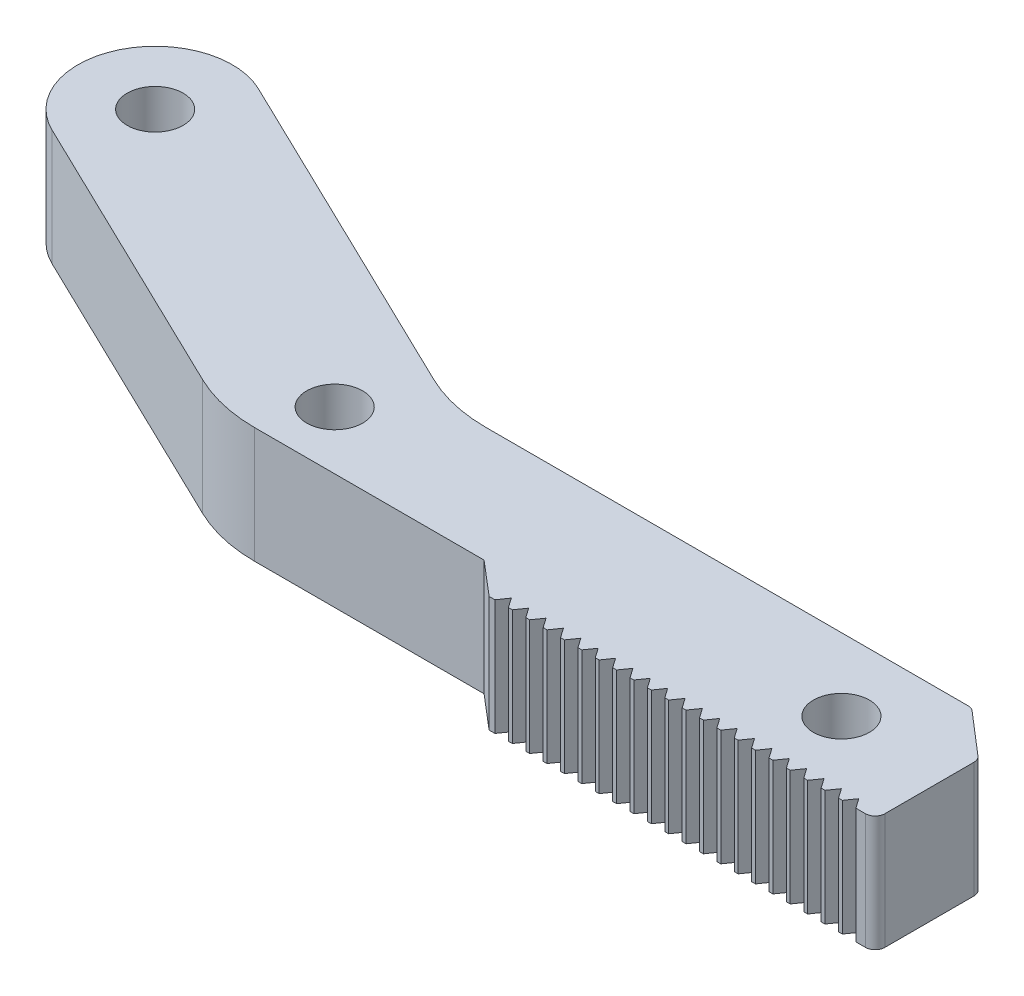
SolidWorks part; units mm, degrees
ref_plane "Alzado" through (0, 0, 0) normal (0, 0, 1) x (1, 0, 0)
ref_plane "Planta" through (0, 0, 0) normal (0, 1, 0) x (1, 0, 0)
ref_plane "Vista lateral" through (0, 0, 0) normal (1, 0, 0) x (0, 0, -1)
sketch "Croquis base" plane through (0, 0, 0) normal (0, 1, 0) x (1, 0, 0)
  line L0 (16.2564, 0) -> (-16.2436, 0) construction
  line L1 (-5.5056, -3) -> (-16.2436, -3)
  line L2 (16.2564, -3) -> (16.2564, 0.85)
  line L3 (13.7564, 3) -> (-13.2589, 3)
  line L5 (-16.2436, 0) -> (-34.25, 8.7046) construction
  line L6 (-16.2436, 0) -> (-34.25, 0) construction
  line L7 (-32.5091, 12.3059) -> (-13.2589, 3)
  line L8 (-35.9909, 5.1033) -> (-19.2283, -3)
  line L9 (-16.2436, -3) -> (-19.2283, -3)
  line L10 (16.2564, -3) -> (16.2564, -4.5)
  line L11 (16.2564, -4.5) -> (-3.7436, -4.5) construction
  line L12 (-3.7436, -4.5) -> (-3.7436, -3) construction
  line L13 (15.2564, -4.5) -> (14.9064, -4)
  line L14 (14.9064, -4) -> (14.5564, -4.5)
  line L15 (15.2564, -4.5) -> (16.2564, -4.5)
  line L16 (14.5564, -4.5) -> (14.3564, -4.5)
  line L17 (14.0064, -4) -> (13.6564, -4.5)
  line L18 (13.6564, -4.5) -> (13.4564, -4.5)
  line L19 (14.3564, -4.5) -> (14.0064, -4)
  line L20 (13.1064, -4) -> (12.7564, -4.5)
  line L21 (12.7564, -4.5) -> (12.5564, -4.5)
  line L22 (13.4564, -4.5) -> (13.1064, -4)
  line L23 (12.2064, -4) -> (11.8564, -4.5)
  line L24 (11.8564, -4.5) -> (11.6564, -4.5)
  line L25 (12.5564, -4.5) -> (12.2064, -4)
  line L26 (11.3064, -4) -> (10.9564, -4.5)
  line L27 (10.9564, -4.5) -> (10.7564, -4.5)
  line L28 (11.6564, -4.5) -> (11.3064, -4)
  line L29 (10.4064, -4) -> (10.0564, -4.5)
  line L30 (10.0564, -4.5) -> (9.8564, -4.5)
  line L31 (10.7564, -4.5) -> (10.4064, -4)
  line L32 (9.5064, -4) -> (9.1564, -4.5)
  line L33 (9.1564, -4.5) -> (8.9564, -4.5)
  line L34 (9.8564, -4.5) -> (9.5064, -4)
  line L35 (8.6064, -4) -> (8.2564, -4.5)
  line L36 (8.2564, -4.5) -> (8.0564, -4.5)
  line L37 (8.9564, -4.5) -> (8.6064, -4)
  line L38 (7.7064, -4) -> (7.3564, -4.5)
  line L39 (7.3564, -4.5) -> (7.1564, -4.5)
  line L40 (8.0564, -4.5) -> (7.7064, -4)
  line L41 (6.8064, -4) -> (6.4564, -4.5)
  line L42 (6.4564, -4.5) -> (6.2564, -4.5)
  line L43 (7.1564, -4.5) -> (6.8064, -4)
  line L44 (5.9064, -4) -> (5.5564, -4.5)
  line L45 (5.5564, -4.5) -> (5.3564, -4.5)
  line L46 (6.2564, -4.5) -> (5.9064, -4)
  line L47 (5.0064, -4) -> (4.6564, -4.5)
  line L48 (4.6564, -4.5) -> (4.4564, -4.5)
  line L49 (5.3564, -4.5) -> (5.0064, -4)
  line L50 (4.1064, -4) -> (3.7564, -4.5)
  line L51 (3.7564, -4.5) -> (3.5564, -4.5)
  line L52 (4.4564, -4.5) -> (4.1064, -4)
  line L53 (3.2064, -4) -> (2.8564, -4.5)
  line L54 (2.8564, -4.5) -> (2.6564, -4.5)
  line L55 (3.5564, -4.5) -> (3.2064, -4)
  line L56 (2.3064, -4) -> (1.9564, -4.5)
  line L57 (1.9564, -4.5) -> (1.7564, -4.5)
  line L58 (2.6564, -4.5) -> (2.3064, -4)
  line L59 (1.4064, -4) -> (1.0564, -4.5)
  line L60 (1.0564, -4.5) -> (0.8564, -4.5)
  line L61 (1.7564, -4.5) -> (1.4064, -4)
  line L62 (0.5064, -4) -> (0.1564, -4.5)
  line L63 (0.1564, -4.5) -> (-0.0436, -4.5)
  line L64 (0.8564, -4.5) -> (0.5064, -4)
  line L65 (-0.3936, -4) -> (-0.7436, -4.5)
  line L66 (-0.7436, -4.5) -> (-0.9436, -4.5)
  line L67 (-0.0436, -4.5) -> (-0.3936, -4)
  line L68 (-1.2936, -4) -> (-1.6436, -4.5)
  line L69 (-1.6436, -4.5) -> (-1.8436, -4.5)
  line L70 (-0.9436, -4.5) -> (-1.2936, -4)
  line L71 (-2.1936, -4) -> (-2.5436, -4.5)
  line L72 (-2.5436, -4.5) -> (-2.7436, -4.5)
  line L73 (-1.8436, -4.5) -> (-2.1936, -4)
  line L74 (-3.0936, -4) -> (-3.4436, -4.5)
  line L75 (-3.4436, -4.5) -> (-3.6436, -4.5)
  line L76 (-2.7436, -4.5) -> (-3.0936, -4)
  line L77 (14.9064, -4) -> (14.0064, -4) construction
  line L78 (-3.6436, -4.5) -> (-3.7436, -4.5)
  line L79 (-3.7436, -4.5) -> (-5.5056, -3)
  line L80 (16.2564, -4.5) -> (16.2564, -3)
  line L81 (-5.5056, -3) -> (16.2564, -3) construction
  line L82 (13.7564, 3) -> (16.2564, 0.85)
  arc A0 (-32.5091, 12.3059) -> (-35.9909, 5.1033) centre (-34.25, 8.7046) ccw
  circle A1 centre (-34.25, 8.7046) radius 1.45
  circle A2 centre (-16.2436, 0) radius 1.45
  circle A3 centre (10.7564, -0.75) radius 1.45
  point P0 (0, 0)
  dimension "D8" = 21.3815
  dimension "D9" = 4
  dimension "D19" = 2.9
  dimension "D1" = 6
  dimension "D2" = 32.5
  dimension "D3" = 20
  dimension "D4" = 18.0064
  dimension "D5" = 25.8
  dimension "D6" = 8
  dimension "D7" = 4
  dimension "D10" = 1.5
  dimension "D11" = 20
  dimension "D12" = 1
  dimension "D13" = 0.7
  dimension "D14" = 0.2
  dimension "D15" = 0.5
  dimension "D17" = 0.9
  dimension "D18" = 1.762
  dimension "D20" = 5.5
  dimension "D21" = 2.25
  dimension "D22" = 2.5
  dimension "D23" = 2.15
  dimension "D16" = 21
extrude "Saliente-Extruir1" add sketch "Croquis base" along normal blind 6 contours L7 A0 L8 L9 L1 L79 L78 L75 L74 L76 L72 L71 L73 L69 L68 L70 L66 L65 L67 L63 L62 L64 L60 L59 L61 L57 L56 L58 L54 L53 L55 L51 L50 L52 L48 L47 L49 L45 L44 L46 L42 L41 L43 L39 L38 L40 L36 L35 L37 L33 L32 region at (-11.8263, 0, -1.9936)
fillet "Redondeo2" radius 8 2 edges at (-13.2589, 3, -3) (-19.2283, 3, 3)
fillet "Redondeo1" radius 0.5 3 edges at (16.2564, 3, 4.5) (13.7564, 3, -3) (16.2564, 3, -0.85)
ref_point "lfinger_cf_center"
ref_plane "lfinger_spin_plain" through (0, 0, -8.7046) normal (0, 0, 1) x (1, 0, 0)
ref_axis "lfinger_spin_axis" through (-34.25, -0.9866, -8.7046) along (0, 1, 0)
